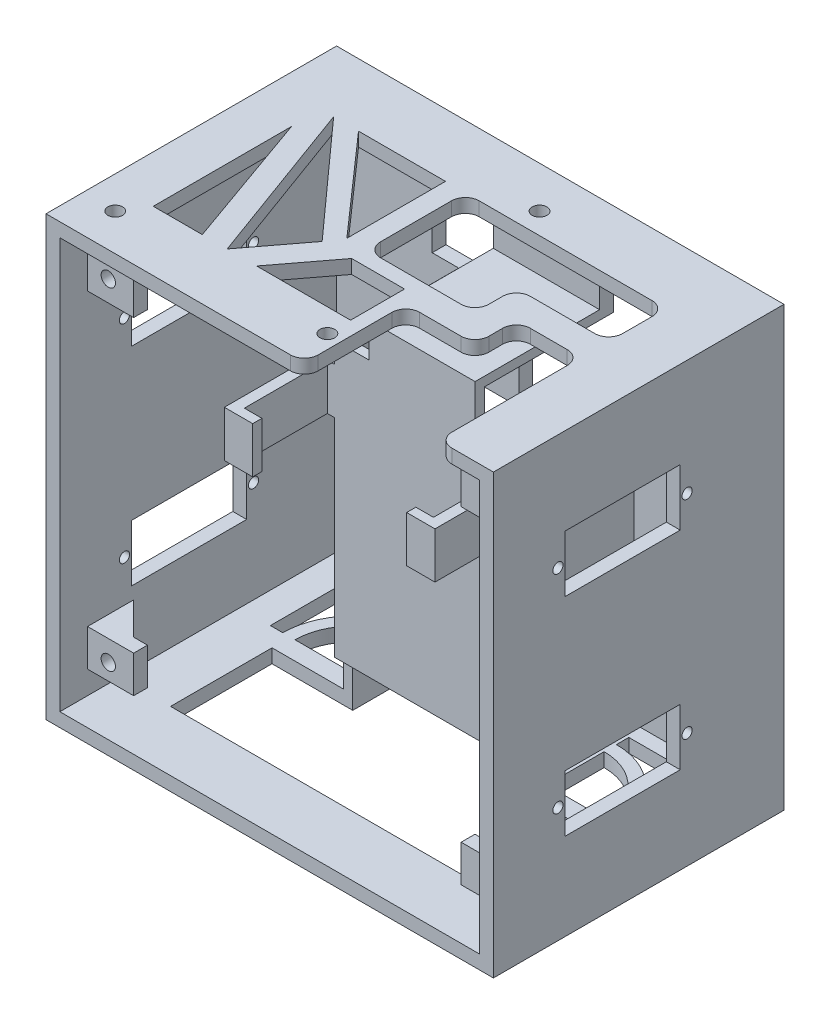
SolidWorks part; units mm, degrees
ref_plane "前视基准面" through (0, 0, 0) normal (0, 0, 1) x (1, 0, 0)
ref_plane "上视基准面" through (0, 0, 0) normal (0, 1, 0) x (1, 0, 0)
ref_plane "右视基准面" through (0, 0, 0) normal (1, 0, 0) x (0, 0, -1)
other "Configuration Table"
sketch "草图1" plane through (0, 0, 0) normal (0, 0, 1) x (1, 0, 0)
  line L1 (0, 0) -> (97, 0)
  line L2 (0, 0) -> (0, 95)
  line L3 (0, 95) -> (97, 95)
  line L4 (97, 0) -> (97, 95)
  dimension "D1" = 97
  dimension "D2" = 95
extrude "凸台-拉伸1" add sketch "草图1" along normal blind 3
sketch "草图2" plane through (0, 0, 3) normal (0, 0, 1) x (1, 0, 0)
  line L1 (0, 95) -> (97, 95)
  line L2 (0, 95) -> (0, 0)
  line L3 (0, 0) -> (97, 0)
  line L4 (97, 95) -> (97, 0)
  line L5 (3, 92) -> (94, 92)
  line L6 (3, 92) -> (3, 3)
  line L7 (3, 3) -> (94, 3)
  line L8 (94, 92) -> (94, 3)
  dimension "D1" = 3
  dimension "D2" = 3
  dimension "D3" = 3
  dimension "D4" = 3
extrude "凸台-拉伸2" add sketch "草图2" along normal blind 60
sketch "草图3" plane through (0, 0, 0) normal (0, 0, -1) x (-1, 0, 0)
  line L0 (-48.5, 95) -> (-48.5, -24.4492) construction
  line L1 (-97, 95) -> (0, 95) construction
  line L2 (0, 0) -> (-97, 0) construction
  line L3 (-65.5, 75) -> (-31.5, 75)
  line L4 (-65.5, 75) -> (-65.5, 0)
  line L5 (-65.5, 0) -> (-31.5, 0)
  line L6 (-31.5, 75) -> (-31.5, 0)
  dimension "D1" = 20
  dimension "D2" = 34
extrude "切除-拉伸1" cut sketch "草图3" against normal blind 30
sketch "草图4" plane through (0, 0, 3) normal (0, 0, 1) x (1, 0, 0)
  line L0 (0, 0) -> (97, 0) construction
  line L1 (29.5, 77) -> (67.5, 77)
  line L2 (29.5, 77) -> (29.5, 0)
  line L3 (29.5, 0) -> (31.5, 0)
  line L4 (67.5, 77) -> (67.5, 0)
  line L5 (65.5, 75) -> (65.5, 3) construction
  line L6 (31.5, 75) -> (65.5, 75) construction
  line L7 (31.5, 3) -> (31.5, 75) construction
  line L8 (65.5, 0) -> (67.5, 0)
  line L13 (65.5, 75) -> (31.5, 75)
  line L14 (65.5, 75) -> (65.5, 0)
  line L16 (31.5, 75) -> (31.5, 0)
  dimension "D1" = 2
  dimension "D2" = 2
  dimension "D3" = 2
extrude "凸台-拉伸3" add sketch "草图4" along normal blind 27
sketch "草图5" plane through (0, 0, 30) normal (0, 0, 1) x (1, 0, 0)
  line L0 (0, 0) -> (97, 0) construction
  line L1 (29.5, 77) -> (66.5, 77)
  line L2 (29.5, 77) -> (29.5, 0)
  line L3 (29.5, 0) -> (66.5, 0)
  line L4 (66.5, 77) -> (66.5, 0)
extrude "凸台-拉伸4" add sketch "草图5" against normal blind 2
sketch "草图6" plane through (0, 0, 0) normal (0, 0, -1) x (-1, 0, 0)
  line L0 (-65.5, 75) -> (-65.5, 0) construction
  line L1 (-65.5, 65) -> (-54.5, 65)
  line L2 (-65.5, 65) -> (-65.5, 50)
  line L3 (-65.5, 50) -> (-54.5, 50)
  line L4 (-54.5, 65) -> (-54.5, 50)
  line L5 (-48.5, 75) -> (-48.5, 28.2472) construction
  line L6 (-31.5, 75) -> (-65.5, 75) construction
  line L7 (-31.5, 75) -> (-65.5, 75) construction
  line L8 (-31.5, 50) -> (-42.5, 50)
  line L9 (-42.5, 65) -> (-42.5, 50)
  line L10 (-31.5, 65) -> (-42.5, 65)
  line L11 (-31.5, 65) -> (-31.5, 50)
  line L12 (-65.5, 38) -> (-65.5, 23)
  line L13 (-65.5, 38) -> (-54.5, 38)
  line L14 (-54.5, 38) -> (-54.5, 23)
  line L15 (-65.5, 23) -> (-54.5, 23)
  line L16 (-31.5, 23) -> (-42.5, 23)
  line L17 (-42.5, 38) -> (-42.5, 23)
  line L18 (-31.5, 38) -> (-42.5, 38)
  line L19 (-31.5, 38) -> (-31.5, 23)
  dimension "D1" = 10
  dimension "D2" = 15
  dimension "D3" = 11
  dimension "D5" = 12
  dimension "D4" = 2
extrude "凸台-拉伸5" add sketch "草图6" against normal blind 3 separate body
sketch "草图9" plane through (0, 0, 0) normal (0, 0, -1) x (-1, 0, 0)
  line L0 (-48.5, 75) -> (-48.5, 86.4875) construction
  line L1 (-36.977, 82.4888) -> (-23.7181, 82.4888)
  line L2 (-36.977, 82.4888) -> (-36.977, 69.5456)
  line L3 (-36.977, 69.5456) -> (-23.7181, 69.5456)
  line L4 (-23.7181, 82.4888) -> (-23.7181, 69.5456)
  line L5 (-31.5, 75) -> (-65.5, 75) construction
  line L6 (-60.023, 69.5456) -> (-73.2819, 69.5456)
  line L7 (-73.2819, 82.4888) -> (-73.2819, 69.5456)
  line L8 (-60.023, 82.4888) -> (-73.2819, 82.4888)
  line L9 (-60.023, 82.4888) -> (-60.023, 69.5456)
extrude "切除-拉伸3" cut sketch "草图9" against normal blind 30
sketch "草图10" plane through (0, 0, 0) normal (0, -1, 0) x (1, 0, 0)
  line L0 (48.5, 63) -> (48.5, 53.0075) construction
  line L1 (14, 50) -> (83, 50)
  line L2 (14, 50) -> (14, 28)
  line L3 (14, 28) -> (83, 28)
  line L4 (83, 50) -> (83, 28)
  line L5 (0, 63) -> (97, 63) construction
  line L6 (31.5, 28) -> (65.5, 28) construction
  line L7 (27.5, 24) -> (15, 24)
  line L8 (27.5, 24) -> (27.5, 11.5)
  line L9 (31.5, 28) -> (31.5, 0) construction
  line L10 (12.3363, 24) -> (9.644, 24)
  line L11 (27.5, 24) -> (-2.5153, -6.0153) construction
  line L12 (9.644, 24) -> (9.644, 8.7261)
  line L13 (9.644, 8.7261) -> (15.5646, 14.6468)
  line L14 (12.2261, 6.144) -> (18.1468, 12.0646)
  line L15 (27.5, 6.144) -> (12.2261, 6.144)
  line L16 (27.5, 8.8363) -> (27.5, 6.144)
  line L17 (87.356, 8.7261) -> (81.4354, 14.6468)
  line L18 (87.356, 24) -> (87.356, 8.7261)
  line L19 (84.6637, 24) -> (87.356, 24)
  line L20 (69.5, 8.8363) -> (69.5, 6.144)
  line L21 (69.5, 6.144) -> (84.7739, 6.144)
  line L22 (84.7739, 6.144) -> (78.8532, 12.0646)
  line L23 (69.5, 24) -> (82, 24)
  line L24 (69.5, 24) -> (69.5, 11.5)
  arc A0 (15, 24) -> (27.5, 11.5) centre (27.5, 24) ccw
  arc A1 (12.3363, 24) -> (15.5646, 14.6468) centre (27.5, 24) ccw
  arc A2 (27.5, 8.8363) -> (18.1468, 12.0646) centre (27.5, 24) cw
  arc A3 (84.6637, 24) -> (81.4354, 14.6468) centre (69.5, 24) cw
  arc A4 (69.5, 8.8363) -> (78.8532, 12.0646) centre (69.5, 24) ccw
  arc A5 (82, 24) -> (69.5, 11.5) centre (69.5, 24) cw
  dimension "D3" = 25
  dimension "D1" = 69
  dimension "D2" = 22
  dimension "D4" = 4
  dimension "D5" = 4
  dimension "D6" = 45
extrude "切除-拉伸4" cut sketch "草图10" against normal blind 10
sketch "草图12" plane through (0, 95, 0) normal (0, 1, 0) x (1, 0, 0)
  line L0 (97, -63) -> (0, -63) construction
  line L1 (85, -63) -> (56, -63)
  line L2 (85, -63) -> (85, -41)
  line L3 (71, -41) -> (56, -41)
  line L4 (56, -63) -> (56, -41)
  line L5 (97, -63) -> (97, 0) construction
  line L6 (0, -63) -> (0, 0) construction
  line L7 (7, -9) -> (53, -9) construction
  line L8 (7, -9) -> (7, -55) construction
  line L9 (7, -55) -> (53, -55) construction
  line L10 (53, -9) -> (53, -55) construction
  line L11 (97, 0) -> (0, 0) construction
  line L12 (41.5258, -35) -> (65, -35)
  line L14 (85, -41) -> (85, -32)
  line L15 (85, -32) -> (71, -32)
  line L16 (71, -41) -> (71, -32)
  line L17 (65, -35) -> (65, -26)
  line L18 (65, -26) -> (85, -26)
  line L19 (85, -26) -> (85, -13.608)
  line L20 (85, -13.608) -> (41.5258, -13.608)
  line L21 (41.5258, -13.608) -> (41.5258, -35)
  line L22 (53, -38.2666) -> (41.5258, -38.2666)
  line L23 (41.5258, -38.2666) -> (32.6421, -49.9732)
  line L24 (32.6421, -49.9732) -> (53, -49.9732)
  line L25 (53, -49.9732) -> (53, -38.2666)
  line L26 (37.2213, -35) -> (37.2213, -13.608)
  line L27 (37.2213, -13.608) -> (18.3617, -13.608)
  line L28 (18.3617, -13.608) -> (37.2213, -35)
  line L29 (35.1329, -38.2666) -> (26.2491, -49.9732)
  line L30 (26.2491, -49.9732) -> (12.965, -13.608)
  line L31 (12.965, -13.608) -> (35.1329, -38.2666)
  line L32 (20.8525, -49.9732) -> (10.2252, -20.001)
  line L33 (10.2252, -20.001) -> (10.2252, -49.9732)
  line L34 (10.2252, -49.9732) -> (20.8525, -49.9732)
  circle A0 centre (7, -55) radius 1.6
  circle A1 centre (53, -9) radius 1.6
  circle A2 centre (53, -55) radius 1.6
  dimension "D8" = 3.2
  dimension "D1" = 12
  dimension "D2" = 22
  dimension "D3" = 29
  dimension "D4" = 46
  dimension "D5" = 46
  dimension "D6" = 7
  dimension "D7" = 9
  dimension "D9" = 9
  dimension "D10" = 14
  dimension "D11" = 6
  dimension "D12" = 6
  dimension "D13" = 6
extrude "切除-拉伸5" cut sketch "草图12" against normal blind 5
fillet "圆角1" radius 3 12 edges at (56, 93.5, 63) (85, 93.5, 63) (85, 93.5, 32) (71, 93.5, 32) (71, 93.5, 41) (56, 93.5, 41) (41.5258, 93.5, 35) (41.5258, 93.5, 13.608) (85, 93.5, 13.608) (85, 93.5, 26) (65, 93.5, 26) (65, 93.5, 35)
ref_plane "基准面1" through (0, 65, 0) normal (0, 1, 0) x (1, 0, 0)
sketch "草图13" plane through (0, 65, 0) normal (0, 1, 0) x (1, 0, 0)
  line L0 (48.5, -30) -> (48.5, -42.0858) construction
  line L1 (29.5, -30) -> (28, -30)
  line L2 (29.5, -30) -> (29.5, -28)
  line L3 (29.5, -28) -> (27.6404, -28)
  line L5 (27.6404, -28) -> (25.668, -28)
  line L6 (28, -30) -> (28, -48)
  line L8 (25.668, -28) -> (25.668, -41.0332)
  line L9 (28, -48) -> (31.8119, -48)
  line L10 (25.668, -41.0332) -> (25.668, -50)
  line L11 (25.668, -50) -> (31.8119, -50)
  line L12 (31.8119, -48) -> (31.8119, -50)
  line L13 (29.5, -30) -> (67.5, -30) construction
  line L14 (67.5, -30) -> (69, -30)
  line L15 (67.5, -30) -> (67.5, -28)
  line L16 (67.5, -28) -> (69.3596, -28)
  line L17 (69.3596, -28) -> (71.332, -28)
  line L18 (71.332, -28) -> (71.332, -41.0332)
  line L19 (71.332, -41.0332) -> (71.332, -50)
  line L20 (71.332, -50) -> (65.1881, -50)
  line L21 (65.1881, -48) -> (65.1881, -50)
  line L22 (69, -48) -> (65.1881, -48)
  line L23 (69, -30) -> (69, -48)
  line L24 (14, -28) -> (31.5, -28) construction
  dimension "D1" = 41
  dimension "D2" = 18
  dimension "D3" = 2
extrude "凸台-拉伸6" add sketch "草图13" against normal blind 10
ref_plane "基准面2" through (0, 0, 54) normal (0, 0, 1) x (1, 0, 0)
sketch "草图15" plane through (0, 0, 54) normal (0, 0, 1) x (1, 0, 0)
  line L0 (48.5, 0) -> (48.5, 29.269) construction
  line L1 (0, 0) -> (97, 0) construction
  line L2 (3, 47.5) -> (17.0153, 47.5) construction
  line L3 (3, 92) -> (3, 3) construction
  line L4 (94, 92) -> (3, 92) construction
  line L5 (7.5, 83.5) -> (89.5, 83.5) construction
  line L6 (7.5, 83.5) -> (7.5, 11.5) construction
  line L7 (7.5, 11.5) -> (89.5, 11.5) construction
  line L8 (89.5, 83.5) -> (89.5, 11.5) construction
  line L9 (3, 87) -> (13, 87)
  line L10 (3, 87) -> (3, 79)
  line L11 (3, 79) -> (13, 79)
  line L12 (13, 87) -> (13, 79)
  line L13 (94, 79) -> (84, 79)
  line L14 (84, 87) -> (84, 79)
  line L15 (94, 87) -> (84, 87)
  line L16 (94, 87) -> (94, 79)
  line L17 (94, 8) -> (94, 16)
  line L18 (94, 8) -> (84, 8)
  line L19 (84, 8) -> (84, 16)
  line L20 (94, 16) -> (84, 16)
  line L21 (3, 16) -> (13, 16)
  line L22 (13, 8) -> (13, 16)
  line L23 (3, 8) -> (13, 8)
  line L24 (3, 8) -> (3, 16)
  circle A0 centre (7.5, 83.5) radius 1.55
  circle A1 centre (89.5, 83.5) radius 1.55
  circle A2 centre (7.5, 11.5) radius 1.55
  circle A3 centre (89.5, 11.5) radius 1.55
  dimension "D3" = 3.1
  dimension "D1" = 82
  dimension "D2" = 72
  dimension "D4" = 5
  dimension "D5" = 8
  dimension "D6" = 10
extrude "凸台-拉伸8" add sketch "草图15" along normal blind 3
chamfer "倒角1" distance 7 angle 45 6 edges at (94, 83, 54) (94, 12, 54) (3, 12, 54) (3, 83, 54) (67.5, 60, 28) (29.5, 60, 28)
sketch "草图16" plane through (0, 0, 0) normal (-1, 0, 0) x (0, 0, 1)
  line L0 (63, 47.5) -> (-7.6526, 47.5) construction
  line L1 (49, 70) -> (21, 70) construction
  line L2 (49, 70) -> (49, 25) construction
  line L3 (49, 25) -> (21, 25) construction
  line L4 (21, 70) -> (21, 25) construction
  line L5 (63, 95) -> (63, 0) construction
  line L6 (35, 25) -> (35, 43.396) construction
  line L8 (47.5, 76.15) -> (22.5, 76.15)
  line L9 (47.5, 76.15) -> (47.5, 63.85)
  line L10 (47.5, 63.85) -> (22.5, 63.85)
  line L11 (22.5, 76.15) -> (22.5, 63.85)
  line L12 (47.5, 31.15) -> (22.5, 31.15)
  line L13 (22.5, 18.85) -> (22.5, 31.15)
  line L14 (47.5, 18.85) -> (22.5, 18.85)
  line L15 (47.5, 18.85) -> (47.5, 31.15)
  circle A0 centre (49, 25) radius 1.1
  circle A1 centre (21, 25) radius 1.1
  circle A2 centre (21, 70) radius 1.1
  circle A3 centre (49, 70) radius 1.1
  dimension "D4" = 2.2
  dimension "D1" = 28
  dimension "D2" = 45
  dimension "D3" = 14
  dimension "D5" = 12.3
  dimension "D6" = 25
extrude "切除-拉伸6" cut sketch "草图16" against normal blind 20
sketch "草图17" plane through (94, 0, 0) normal (-1, 0, 0) x (0, 0, 1)
  line L0 (47.5, 18.85) -> (47.5, 31.15) construction
  line L1 (22.5, 18.85) -> (47.5, 18.85) construction
  line L2 (22.5, 31.15) -> (22.5, 18.85) construction
  line L3 (47.5, 31.15) -> (22.5, 31.15) construction
  line L4 (22.5, 63.85) -> (47.5, 63.85) construction
  line L5 (47.5, 63.85) -> (47.5, 76.15) construction
  line L6 (22.5, 76.15) -> (22.5, 63.85) construction
  line L7 (47.5, 76.15) -> (22.5, 76.15) construction
  line L8 (47.5, 18.85) -> (47.5, 31.15)
  line L9 (22.5, 18.85) -> (47.5, 18.85)
  line L10 (22.5, 31.15) -> (22.5, 18.85)
  line L11 (47.5, 31.15) -> (22.5, 31.15)
  line L12 (22.5, 63.85) -> (47.5, 63.85)
  line L13 (47.5, 63.85) -> (47.5, 76.15)
  line L14 (22.5, 76.15) -> (22.5, 63.85)
  line L15 (47.5, 76.15) -> (22.5, 76.15)
  circle A0 centre (49, 25) radius 1.1 construction
  circle A1 centre (21, 25) radius 1.1 construction
  circle A2 centre (49, 70) radius 1.1 construction
  circle A3 centre (21, 70) radius 1.1 construction
  circle A4 centre (49, 25) radius 1.1
  circle A5 centre (21, 25) radius 1.1
  circle A6 centre (49, 70) radius 1.1
  circle A7 centre (21, 70) radius 1.1
extrude "切除-拉伸7" cut sketch "草图17" against normal blind 3
sketch "草图18" plane through (0, 0, 0) normal (0, 0, -1) x (-1, 0, 0)
  line L0 (-48.5, 0) -> (-48.5, 5.9869) construction
  line L1 (-54.5, 23) -> (-69.5, 23)
  line L2 (-54.5, 23) -> (-54.5, 38)
  line L3 (-54.5, 38) -> (-69.5, 38)
  line L4 (-69.5, 23) -> (-69.5, 38)
  line L5 (-83, 0) -> (-14, 0) construction
  line L6 (-42.5, 38) -> (-27.5, 38)
  line L7 (-27.5, 23) -> (-27.5, 38)
  line L8 (-42.5, 23) -> (-27.5, 23)
  line L9 (-42.5, 23) -> (-42.5, 38)
  line L10 (-54.5, 38) -> (-65.5, 38) construction
  dimension "D1" = 15
extrude "凸台-拉伸9" add sketch "草图18" along normal blind 4
sketch "草图19" plane through (0, 23, 0) normal (0, -1, 0) x (1, 0, 0)
  line L0 (31.5, 28) -> (31.5, 0) construction
  line L1 (31.5, 1.0748) -> (38.5, 1.0748)
  line L2 (31.5, 1.0748) -> (31.5, -1.9252)
  line L3 (31.5, -1.9252) -> (38.5, -1.9252)
  line L4 (38.5, 1.0748) -> (38.5, -1.9252)
  line L5 (48.5, 0) -> (48.5, -12.0575) construction
  line L6 (36.977, 0) -> (60.023, 0) construction
  line L7 (65.5, -1.9252) -> (58.5, -1.9252)
  line L8 (58.5, 1.0748) -> (58.5, -1.9252)
  line L9 (65.5, 1.0748) -> (58.5, 1.0748)
  line L10 (65.5, 1.0748) -> (65.5, -1.9252)
  dimension "D1" = 3
  dimension "D2" = 7
extrude "切除-拉伸8" cut sketch "草图19" against normal blind 9
fillet "圆角2" radius 10 2 edges at (69.5, 30.5, 0) (27.5, 30.5, 0)
